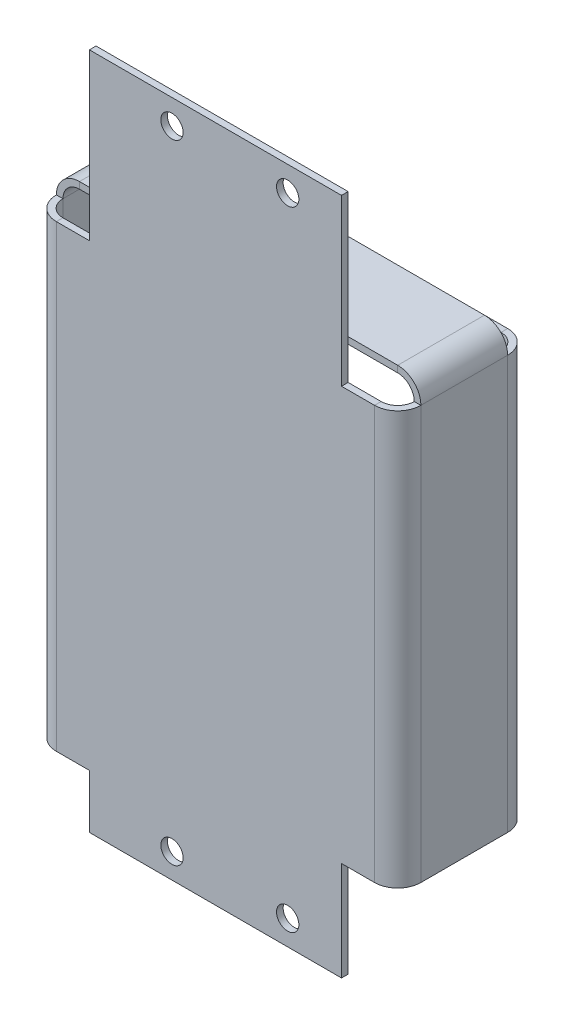
SolidWorks part; units mm, degrees
note: The reader was unsure of these and kept them because the rebuilt part matched: flange length of "Edge-Flange1", "Edge-Flange4", "Edge-Flange5".
ref_plane "Front Plane" through (0, 0, 0) normal (0, 0, 1) x (1, 0, 0)
ref_plane "Top Plane" through (0, 0, 0) normal (0, 1, 0) x (1, 0, 0)
ref_plane "Right Plane" through (0, 0, 0) normal (1, 0, 0) x (0, 0, -1)
sketch "Sketch1" plane through (0, 0, 0) normal (0, 0, 1) x (1, 0, 0)
  line L0 (15.25, 0) -> (15.25, -12)
  line L1 (21.25, 50) -> (15.25, 50)
  line L2 (21.25, 50) -> (21.25, 0)
  line L3 (21.25, 0) -> (15.25, 0)
  line L4 (-21.25, 50) -> (-21.25, -5.5)
  line L5 (15.25, -12) -> (-15.25, -12)
  line L6 (-15.25, -12) -> (-15.25, -5.5)
  line L7 (15.25, 50) -> (15.25, 70)
  line L9 (15.25, 70) -> (-15.25, 70)
  line L10 (-15.25, 70) -> (-15.25, 50)
  line L11 (-15.25, -5.5) -> (-21.25, -5.5)
  line L12 (-15.25, 50) -> (-21.25, 50)
  circle A0 centre (8.7378, -9) radius 1.35
  circle A1 centre (-5.2622, -9) radius 1.35
  circle A2 centre (8.7378, 67) radius 1.35
  circle A3 centre (-5.2622, 67) radius 1.35
  dimension "D6" = 6.5122
  dimension "D7" = 3
  dimension "D8" = 2.7
  dimension "D9" = 3
  dimension "D10" = 14
  dimension "D11" = 76
  dimension "D12" = 14
  dimension "D13" = 3
  dimension "D14" = 3
  dimension "D1" = 50
  dimension "D2" = 42.5
  dimension "D3" = 82
  dimension "D4" = 12
  dimension "D5" = 30.5
  dimension "D15" = 6.5
sheet metal parameters "Sheet-Metal1" thickness 0.8 parameters "D1"=2
base flange "Base-Flange1" sketch "Sketch1" thickness 0.8 reverse thickness direction yes parameters "D1"=2
edge flange "Edge-Flange1" sketch "Sketch6" flange profiles "Sketch6", "Sketch11" flange angle 90 flange length 12.5 flange position material outside bend radius 2 thickness 0.8 parameters "D6"=10, "D8"=1
sketch "Sketch6" plane through (21.25, 0, 0) normal (-1, 0, 0) x (0, 1, 0)
  line L2 (0, 0) -> (0, 12.5)
  line L3 (0, 12.5) -> (50, 12.5)
  line L4 (50, 12.5) -> (50, 0)
  line L6 (50, 0) -> (0, 0) construction
  line L7 (50, 0) -> (0, 0)
sketch "Sketch11" plane through (-21.25, 0, 0) normal (1, 0, 0) x (0, -1, 0)
  line L0 (5.5, 0) -> (-50, 0) construction
  line L1 (5.5, 0) -> (-50, 0)
  line L2 (5.5, 0) -> (5.5, 12.5)
  line L3 (5.5, 12.5) -> (-50, 12.5)
  line L4 (-50, 12.5) -> (-50, 0)
bend "EdgeBend1" bend radius 2 bend angle 90 parameters "D5"=1
bend "EdgeBend3" bend radius 2 bend angle 90 parameters "D5"=2
edge flange "Edge-Flange4" sketch "Sketch19" flange profiles "Sketch19", "Sketch20" flange angle 90 flange length 20 flange position bend outside bend radius 2 thickness 0.8 parameters "D6"=10, "D8"=1
sketch "Sketch19" plane through (21.25, 50, 0) normal (0, -1, 0) x (0, 0, 1)
  line L2 (-12.5, 0) -> (-12.5, 20)
  line L3 (-12.5, 20) -> (-2, 20)
  line L4 (-2, 20) -> (-2, 0)
  line L6 (-2, 0) -> (-12.5, 0) construction
  line L7 (-2, 0) -> (-12.5, 0)
sketch "Sketch20" plane through (-21.25, 50, 0) normal (0, -1, 0) x (0, 0, -1)
  line L0 (12.5, 0) -> (2, 0) construction
  line L1 (12.5, 0) -> (2, 0)
  line L2 (12.5, 0) -> (12.5, 20)
  line L3 (12.5, 20) -> (2, 20)
  line L4 (2, 20) -> (2, 0)
bend "EdgeBend5" bend radius 2 bend angle 90 parameters "D5"=3
bend "EdgeBend6" bend radius 2 bend angle 90 parameters "D5"=4
edge flange "Edge-Flange5" sketch "Sketch28" flange profiles "Sketch28", "Sketch29" flange angle 90 flange length 10 flange position bend outside bend radius 2 thickness 0.8 parameters "D6"=10, "D8"=1
sketch "Sketch28" plane through (21.25, 0, -12.5) normal (0, 0, 1) x (0, 1, 0)
  line L1 (50, 0) -> (0, 0) construction
  line L2 (0, 0) -> (0, 10)
  line L3 (0, 10) -> (50, 10)
  line L4 (50, 10) -> (50, 0)
  line L5 (50, 0) -> (0, 0)
sketch "Sketch29" plane through (-21.25, 0, -12.5) normal (0, 0, 1) x (0, -1, 0)
  line L0 (5.5, 0) -> (-50, 0) construction
  line L1 (5.5, 0) -> (-50, 0)
  line L2 (5.5, 0) -> (5.5, 10)
  line L3 (5.5, 10) -> (-50, 10)
  line L4 (-50, 10) -> (-50, 0)
bend "EdgeBend7" bend radius 2 bend angle 90 parameters "D5"=5
bend "EdgeBend8" bend radius 2 bend angle 90 parameters "D5"=6
flat pattern "Flat-Pattern1" [suppressed]
sketch "Bend-Lines1" plane through (0, 0, 0.8) normal (0, 0, 1) x (1, 0, 0)
  line L0 (-35.3766, -5.5) -> (-35.3766, 50) construction
  line L1 (35.3766, 50) -> (35.3766, 0) construction
  line L2 (-33.5011, 51.8755) -> (-23.0011, 51.8755) construction
  line L3 (23.0011, 51.8755) -> (33.5011, 51.8755) construction
  line L4 (-21.1255, -5.5) -> (-21.1255, 50) construction
  line L5 (21.1255, 50) -> (21.1255, 0) construction
  line L6 (-35.3766, -5.5) -> (-35.3766, 50) construction
  line L7 (35.3766, 50) -> (35.3766, 0) construction
  line L8 (-33.5011, 51.8755) -> (-23.0011, 51.8755) construction
  line L9 (23.0011, 51.8755) -> (33.5011, 51.8755) construction
  line L10 (-21.1255, -5.5) -> (-21.1255, 50) construction
  line L11 (21.1255, 50) -> (21.1255, 0) construction
sketch3d "Bounding-Box1" [suppressed]
  line L0 (-66.5021, -12, 0) -> (24.0021, -12, 0) construction
  line L1 (-66.5021, 71.7511, 0) -> (24.0021, 71.7511, 0) construction
  line L2 (-66.5021, -12, 0) -> (-66.5021, 71.7511, 0) construction
  line L3 (24.0021, -12, 0) -> (24.0021, 71.7511, 0) construction
bend of the flat pattern "Flatten-<EdgeBend1>1"
bend of the flat pattern "Flatten-<EdgeBend3>1"
bend of the flat pattern "Flatten-<EdgeBend5>1"
bend of the flat pattern "Flatten-<EdgeBend6>1"
bend of the flat pattern "Flatten-<EdgeBend7>1"
bend of the flat pattern "Flatten-<EdgeBend8>1"
fillet "Fillet1" [suppressed] radius 1.88
